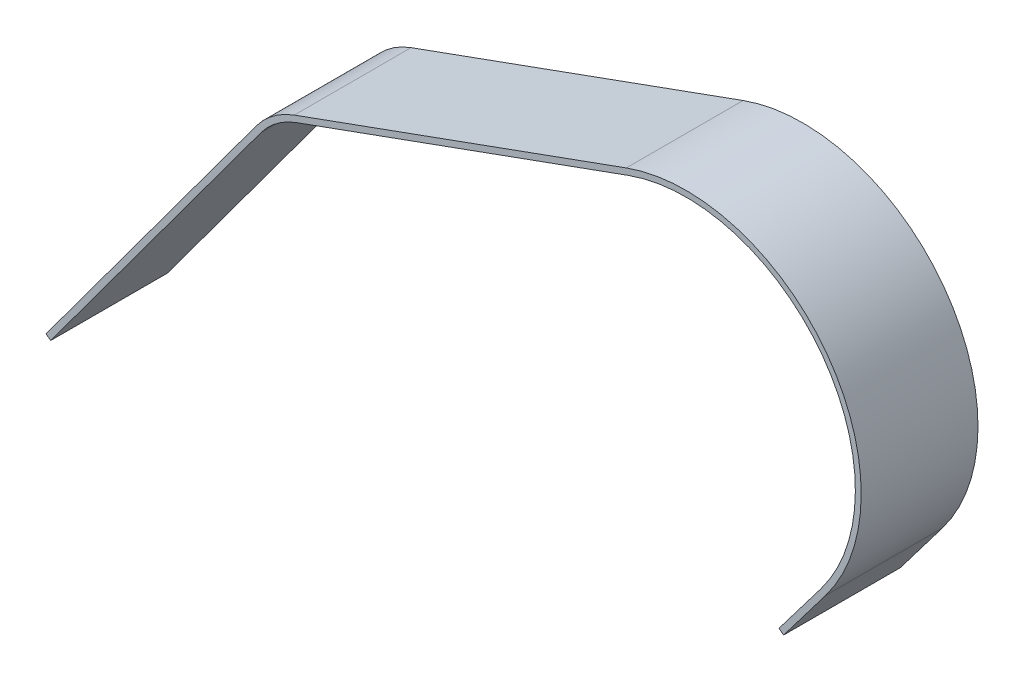
SolidWorks part; units mm, degrees
material "AISI 1020"
ref_plane "Front Plane" through (0, 0, 0) normal (0, 0, 1) x (1, 0, 0)
ref_plane "Top Plane" through (0, 0, 0) normal (0, 1, 0) x (1, 0, 0)
ref_plane "Right Plane" through (0, 0, 0) normal (1, 0, 0) x (0, 0, -1)
sketch "Sketch1" plane through (0, 0, 0) normal (0, 0, 1) x (1, 0, 0)
  line L0 (-36.5682, 0.9207) -> (143.9526, 66.3011)
  line L1 (-21.4316, -40.8727) -> (13.1807, -28.3369) construction
  line L6 (-36.5682, 0.9207) -> (-21.4316, -40.8727) construction
  line L14 (229.4691, -110.8747) -> (252.2647, -80.8348)
  line L15 (239.0655, -98.2286) -> (240.3301, -99.1882) construction
  line L19 (-57.2078, -14.4934) -> (-171.5307, -169.5402)
  line L23 (-163.3872, -155.8209) -> (-162.1095, -156.763) construction
  line L28 (143.9526, 66.3011) -> (194.1881, -72.4034) construction
  arc A0 (-57.2078, -14.4934) -> (-36.5682, 0.9207) centre (-21.4316, -40.8727) cw
  arc A10 (-190.1171, -186.0404) -> (-190.1067, -160.6404) centre (-190.1119, -173.3404) ccw construction
  arc A11 (143.9526, 66.3011) -> (252.2647, -80.8348) centre (176.3881, -23.2561) cw
  circle A12 centre (-21.4316, -40.8727) radius 6 construction
  circle A13 centre (231.071, -129.7727) radius 12.7 construction
  dimension "D5" = 44.45
  dimension "D3" = 15.875
  dimension "D2" = 95.25
  dimension "D1" = 15.875
extrude "Extrude-Thin1" add sketch "Sketch1" along normal blind 63.5 thin thin type one direction reverse wall 3.175
sketch "Sketch2" plane through (199.0077, -151.0163, 0) normal (0.7966, -0.6045, 0) x (0, 0, -1)
  line L0 (-31.75, 88.1008) -> (-31.75, 50.3909) construction
  line L1 (-63.5, 88.1008) -> (0, 88.1008) construction
  line L2 (-63.5, 50.3909) -> (0, 50.3909) construction
